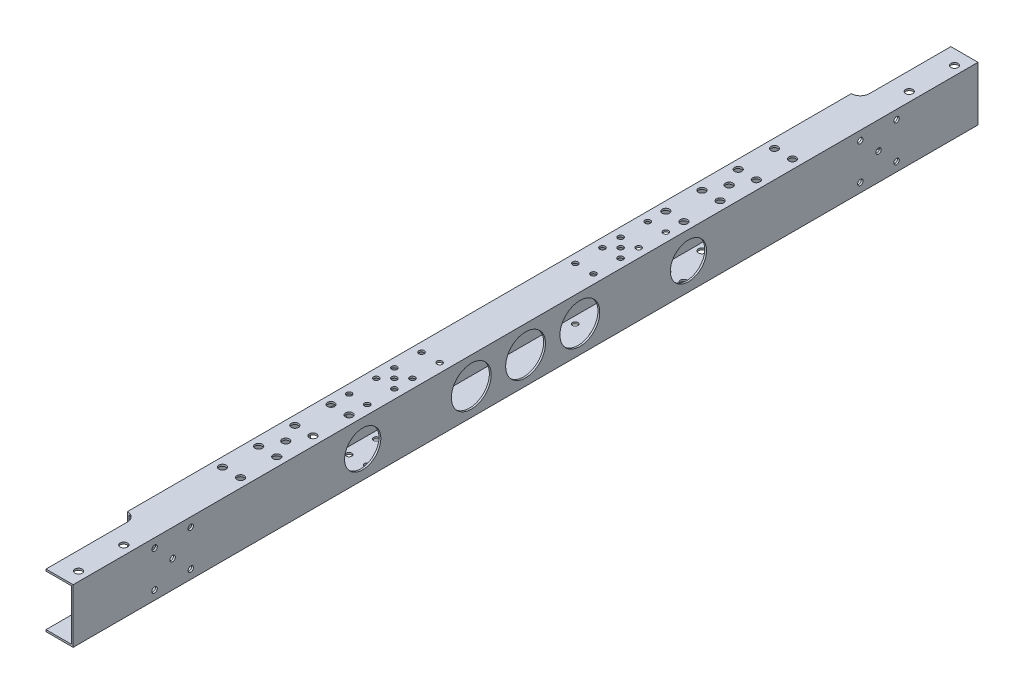
SolidWorks part; units mm, degrees
material "6061-T4 (SS)"
ref_plane "前视基准面" through (0, 0, 0) normal (0, 0, 1) x (1, 0, 0)
ref_plane "上视基准面" through (0, 0, 0) normal (0, 1, 0) x (1, 0, 0)
ref_plane "右视基准面" through (0, 0, 0) normal (1, 0, 0) x (0, 0, -1)
other "Configuration Table"
sketch "草图1" plane through (0, 0, 0) normal (0, 0, 1) x (1, 0, 0)
  line L1 (-10, -15) -> (10, -15)
  line L2 (-10, -15) -> (-10, 15)
  line L3 (-10, 15) -> (10, 15)
  line L4 (10, -15) -> (10, 15)
  line L5 (-10, -15) -> (10, 15) construction
  line L6 (-10, 15) -> (10, -15) construction
  point P0 (0, 0)
  dimension "D1" = 20
  dimension "D2" = 30
extrude "拉伸-薄壁1" add sketch "草图1" along normal blind 500 thin thin type one direction reverse wall 1
sketch "草图2" plane through (0, 15, 0) normal (0, 1, 0) x (1, 0, 0)
  line L0 (-5, -317.5) -> (5, -307.5) construction
  line L1 (-10, -500) -> (-10, 0) construction
  line L2 (0, -187.5) -> (0, -312.5) construction
  line L3 (0, -250) -> (-10, -250) construction
  line L4 (-5, -192.5) -> (5, -192.5) construction
  line L5 (-5, -192.5) -> (-5, -182.5) construction
  line L6 (-5, -182.5) -> (5, -182.5) construction
  line L7 (5, -192.5) -> (5, -182.5) construction
  line L8 (-5, -192.5) -> (5, -182.5) construction
  line L9 (-5, -182.5) -> (5, -192.5) construction
  line L10 (-5, -307.5) -> (5, -317.5) construction
  line L11 (5, -307.5) -> (5, -317.5) construction
  line L12 (-5, -317.5) -> (5, -317.5) construction
  line L13 (-5, -307.5) -> (-5, -317.5) construction
  line L14 (-5, -307.5) -> (5, -307.5) construction
  circle A0 centre (5, -182.5) radius 1.5
  circle A1 centre (5, -192.5) radius 1.5
  circle A2 centre (-5, -192.5) radius 1.5
  circle A3 centre (-5, -182.5) radius 1.5
  circle A4 centre (-5, -317.5) radius 1.5
  circle A5 centre (-5, -307.5) radius 1.5
  circle A6 centre (5, -307.5) radius 1.5
  circle A7 centre (5, -317.5) radius 1.5
  dimension "D3" = 3
  dimension "D1" = 125
  dimension "D2" = 10
  dimension "D4" = 10
extrude "切除-拉伸1" cut sketch "草图2" against normal up to surface (30 mm away) up to face at (0, -15, 250)
sketch "草图4" plane through (0, 15, 0) normal (0, 1, 0) x (1, 0, 0)
  line L0 (-10, -250) -> (52.7857, -250) construction
  line L1 (-10, -500) -> (-10, 0) construction
  line L2 (-5, -500) -> (-5, -450)
  line L3 (-10, 0) -> (-5, 0)
  line L4 (-10, 0) -> (-10, -50)
  line L5 (-10, -50) -> (-5, -50)
  line L6 (-5, 0) -> (-5, -50)
  line L7 (-10, -450) -> (-5, -450)
  line L8 (-10, -500) -> (-10, -450)
  line L9 (-10, -500) -> (-5, -500)
  dimension "D1" = 5
  dimension "D2" = 50
extrude "切除-拉伸3" cut sketch "草图4" against normal up to surface (30 mm away) up to face at (-5, -15, 319)
fillet "圆角1" radius 5 2 edges at (-5, 14.5, 450) (-5, 14.5, 50)
sketch "草图5" plane through (0, 15, 0) normal (0, 1, 0) x (1, 0, 0)
  line L0 (-10, -250) -> (78.9829, -250) construction
  line L1 (-10, -450) -> (-10, -50) construction
  line L2 (0, 0) -> (0, -20.5) construction
  line L3 (10, 0) -> (-5, 0) construction
  line L4 (-5, -33) -> (5, -33) construction
  line L5 (-5, -33) -> (-5, -8) construction
  line L6 (-5, -8) -> (5, -8) construction
  line L7 (5, -33) -> (5, -8) construction
  line L8 (-5, -33) -> (5, -8) construction
  line L9 (-5, -8) -> (5, -33) construction
  line L10 (-5, -492) -> (5, -467) construction
  line L11 (-5, -467) -> (5, -492) construction
  line L12 (5, -467) -> (5, -492) construction
  line L13 (-5, -492) -> (5, -492) construction
  line L14 (-5, -467) -> (-5, -492) construction
  line L15 (-5, -467) -> (5, -467) construction
  line L16 (0, -500) -> (0, -479.5) construction
  circle A0 centre (5, -8) radius 2
  circle A1 centre (5, -33) radius 2
  circle A2 centre (5, -467) radius 2
  circle A3 centre (5, -492) radius 2
  dimension "D2" = 4
  dimension "D1" = 25
  dimension "D3" = 8
  dimension "D4" = 10
extrude "切除-拉伸4" cut sketch "草图5" against normal up to surface (30 mm away) up to face at (-5, -15, 319)
sketch "草图6" plane through (0, 15, 0) normal (0, 1, 0) x (1, 0, 0)
  line L0 (-10, -250) -> (143.2134, -250) construction
  line L1 (-10, -450) -> (-10, -50) construction
  line L2 (-5, -182.5) -> (5, -192.5) construction
  line L3 (0, -187.5) -> (0, -127.5) construction
  line L5 (-5, -342.5) -> (5, -332.5) construction
  line L6 (-5, -137.5) -> (5, -137.5) construction
  line L7 (-5, -137.5) -> (-5, -117.5) construction
  line L8 (-5, -117.5) -> (5, -117.5) construction
  line L9 (5, -137.5) -> (5, -117.5) construction
  line L10 (-5, -137.5) -> (5, -117.5) construction
  line L11 (-5, -117.5) -> (5, -137.5) construction
  line L12 (-5, -157.5) -> (5, -157.5) construction
  line L13 (-5, -157.5) -> (-5, -97.5) construction
  line L14 (-5, -97.5) -> (5, -97.5) construction
  line L15 (5, -157.5) -> (5, -97.5) construction
  line L16 (-5, -157.5) -> (5, -97.5) construction
  line L17 (-5, -97.5) -> (5, -157.5) construction
  line L18 (-5, -167.5) -> (5, -167.5) construction
  line L19 (-5, -167.5) -> (-5, -157.5) construction
  line L20 (-5, -157.5) -> (5, -157.5) construction
  line L21 (5, -167.5) -> (5, -157.5) construction
  line L22 (-5, -167.5) -> (5, -157.5) construction
  line L23 (-5, -157.5) -> (5, -167.5) construction
  line L24 (-5, -332.5) -> (5, -342.5) construction
  line L25 (5, -332.5) -> (5, -342.5) construction
  line L26 (-5, -342.5) -> (5, -342.5) construction
  line L27 (-5, -332.5) -> (-5, -342.5) construction
  line L28 (-5, -332.5) -> (5, -332.5) construction
  line L29 (-5, -402.5) -> (5, -342.5) construction
  line L30 (-5, -342.5) -> (5, -402.5) construction
  line L31 (5, -342.5) -> (5, -402.5) construction
  line L32 (-5, -402.5) -> (5, -402.5) construction
  line L33 (-5, -342.5) -> (-5, -402.5) construction
  line L34 (-5, -342.5) -> (5, -342.5) construction
  line L35 (-5, -382.5) -> (5, -362.5) construction
  line L36 (-5, -362.5) -> (5, -382.5) construction
  line L37 (5, -362.5) -> (5, -382.5) construction
  line L38 (-5, -382.5) -> (5, -382.5) construction
  line L39 (-5, -362.5) -> (-5, -382.5) construction
  line L40 (-5, -362.5) -> (5, -362.5) construction
  line L41 (0, -312.5) -> (0, -372.5) construction
  line L42 (0, -187.5) -> (42.6444, -187.5) construction
  line L43 (-5, -207.5) -> (5, -207.5) construction
  line L44 (-5, -292.5) -> (5, -292.5) construction
  circle A0 centre (5, -97.5) radius 2
  circle A1 centre (5, -117.5) radius 2
  circle A2 centre (5, -137.5) radius 2
  circle A3 centre (5, -157.5) radius 2
  circle A4 centre (-5, -157.5) radius 2
  circle A5 centre (-5, -137.5) radius 2
  circle A6 centre (-5, -117.5) radius 2
  circle A7 centre (-5, -97.5) radius 2
  circle A8 centre (0, -127.5) radius 2
  circle A9 centre (5, -167.5) radius 1.5
  circle A10 centre (-5, -167.5) radius 1.5
  circle A11 centre (5, -182.5) radius 1.5 construction
  circle A12 centre (-5, -332.5) radius 1.5
  circle A13 centre (5, -332.5) radius 1.5
  circle A14 centre (0, -372.5) radius 2
  circle A15 centre (-5, -402.5) radius 2
  circle A16 centre (-5, -382.5) radius 2
  circle A17 centre (-5, -362.5) radius 2
  circle A18 centre (-5, -342.5) radius 2
  circle A19 centre (5, -342.5) radius 2
  circle A20 centre (5, -362.5) radius 2
  circle A21 centre (5, -382.5) radius 2
  circle A22 centre (5, -402.5) radius 2
  circle A23 centre (0, -187.5) radius 1.5
  circle A24 centre (-5, -207.5) radius 1.5
  circle A25 centre (5, -207.5) radius 1.5
  circle A26 centre (5, -292.5) radius 1.5
  circle A27 centre (-5, -292.5) radius 1.5
  circle A28 centre (0, -312.5) radius 1.5
  point P28 (0, -162.5)
  point P58 (0, -337.5)
  dimension "D3" = 4
  dimension "D4" = 3
  dimension "D1" = 20
  dimension "D2" = 60
  dimension "D5" = 10
  dimension "D6" = 15
  dimension "D7" = 10
extrude "切除-拉伸5" cut sketch "草图6" against normal up to surface (30 mm away) up to face at (5, -15, 10)
sketch "草图8" plane through (-10, 0, 0) normal (-1, 0, 0) x (0, 0, 1)
  line L0 (250, 15) -> (250, -72.2485) construction
  line L1 (450, 15) -> (50, 15) construction
  line L2 (50, 0) -> (250, 0) construction
  line L3 (50, -15) -> (50, 15) construction
  circle A0 centre (250, 0) radius 11
  circle A1 centre (280, 0) radius 11
  circle A2 centre (220, 0) radius 11
  dimension "D1" = 22
  dimension "D2" = 30
  dimension "D3" = 30
extrude "切除-拉伸6" cut sketch "草图8" against normal up to surface (20 mm away) up to face at (10, 0, 250)
sketch "草图9" plane through (10, 0, 0) normal (1, 0, 0) x (0, 0, -1)
  line L0 (-250, 0) -> (-250, 28.8218) construction
  line L2 (0, -15) -> (0, 15) construction
  line L3 (-65, -10) -> (-45, -10) construction
  line L4 (-65, -10) -> (-65, 10) construction
  line L5 (-65, 10) -> (-45, 10) construction
  line L6 (-45, -10) -> (-45, 10) construction
  line L7 (-65, -10) -> (-45, 10) construction
  line L8 (-65, 10) -> (-45, -10) construction
  line L9 (-55, 0) -> (0, 0) construction
  line L10 (-435, 10) -> (-455, -10) construction
  line L11 (-435, -10) -> (-455, 10) construction
  line L12 (-455, -10) -> (-455, 10) construction
  line L13 (-435, 10) -> (-455, 10) construction
  line L14 (-435, -10) -> (-435, 10) construction
  line L15 (-435, -10) -> (-455, -10) construction
  line L16 (-250, 0) -> (-160, 0) construction
  circle A0 centre (-250, 0) radius 11 construction
  circle A1 centre (-250, 0) radius 11 construction
  circle A2 centre (-45, 10) radius 1.5
  circle A3 centre (-45, -10) radius 1.5
  circle A4 centre (-65, -10) radius 1.5
  circle A5 centre (-65, 10) radius 1.5
  circle A6 centre (-55, 0) radius 1.5
  circle A7 centre (-445, 0) radius 1.5
  circle A8 centre (-435, 10) radius 1.5
  circle A9 centre (-435, -10) radius 1.5
  circle A10 centre (-455, -10) radius 1.5
  circle A11 centre (-455, 10) radius 1.5
  circle A12 centre (-160, 0) radius 10
  circle A13 centre (-340, 0) radius 10
  point P3 (-55, 0)
  point P29 (-445, 0)
  dimension "D2" = 3
  dimension "D4" = 20
  dimension "D5" = 90
  dimension "D1" = 55
  dimension "D3" = 20
extrude "切除-拉伸7" cut sketch "草图9" against normal up to surface (20 mm away) up to face at (-10, 0, 231)
sketch "草图10" plane through (0, 15, 0) normal (0, 1, 0) x (1, 0, 0)
  line L0 (10, -250) -> (-94.9456, -250) construction
  line L1 (10, -500) -> (10, 0) construction
  line L2 (-5, -97.5) -> (5, -97.5) construction
  line L3 (0, -97.5) -> (0, -82.5) construction
  line L4 (0, -82.5) -> (0, -57.5) construction
  line L5 (-4, -82.5) -> (-4, -57.5)
  line L6 (4, -82.5) -> (4, -57.5)
  line L7 (0, -97.5) -> (0, -109.5) construction
  line L8 (0, -109.5) -> (0, -105.5) construction
  line L9 (-4, -109.5) -> (-4, -105.5)
  line L10 (4, -109.5) -> (4, -105.5)
  line L11 (-5, -117.5) -> (5, -117.5) construction
  line L12 (0, -127.5) -> (39.9087, -127.5) construction
  line L13 (-5, -137.5) -> (5, -137.5) construction
  line L14 (0, -145.5) -> (0, -149.5) construction
  line L15 (-4, -145.5) -> (-4, -149.5)
  line L16 (4, -145.5) -> (4, -149.5)
  line L17 (0, -187.5) -> (36.5278, -187.5) construction
  line L18 (-5, -182.5) -> (5, -182.5) construction
  line L19 (-5, -167.5) -> (5, -167.5) construction
  line L20 (0, -167.5) -> (0, -182.5) construction
  line L21 (0, -332.5) -> (0, -317.5) construction
  line L22 (-5, -332.5) -> (5, -332.5) construction
  line L23 (-5, -317.5) -> (5, -317.5) construction
  line L24 (0, -312.5) -> (36.5278, -312.5) construction
  line L25 (-5, -362.5) -> (5, -362.5) construction
  line L26 (0, -372.5) -> (39.9087, -372.5) construction
  line L27 (-5, -382.5) -> (5, -382.5) construction
  line L28 (0, -402.5) -> (0, -390.5) construction
  line L29 (0, -402.5) -> (0, -417.5) construction
  line L30 (-5, -402.5) -> (5, -402.5) construction
  line L31 (0, -354.5) -> (0, -350.5) construction
  line L32 (-4, -354.5) -> (-4, -350.5)
  line L33 (4, -354.5) -> (4, -350.5)
  line L34 (0, -390.5) -> (0, -394.5) construction
  line L35 (-4, -390.5) -> (-4, -394.5)
  line L36 (4, -390.5) -> (4, -394.5)
  line L37 (0, -417.5) -> (0, -442.5) construction
  line L38 (-4, -417.5) -> (-4, -442.5)
  line L39 (4, -417.5) -> (4, -442.5)
  arc A0 (-4, -82.5) -> (4, -82.5) centre (0, -82.5) ccw
  arc A1 (4, -57.5) -> (-4, -57.5) centre (0, -57.5) ccw
  arc A2 (-4, -109.5) -> (4, -109.5) centre (0, -109.5) ccw
  arc A3 (4, -105.5) -> (-4, -105.5) centre (0, -105.5) ccw
  arc A4 (-4, -145.5) -> (4, -145.5) centre (0, -145.5) cw
  arc A5 (4, -149.5) -> (-4, -149.5) centre (0, -149.5) cw
  circle A6 centre (0, -175) radius 4
  circle A7 centre (0, -200) radius 4
  circle A8 centre (0, -325) radius 4
  arc A9 (-4, -354.5) -> (4, -354.5) centre (0, -354.5) ccw
  arc A10 (4, -350.5) -> (-4, -350.5) centre (0, -350.5) ccw
  arc A11 (-4, -390.5) -> (4, -390.5) centre (0, -390.5) cw
  arc A12 (4, -394.5) -> (-4, -394.5) centre (0, -394.5) cw
  arc A13 (-4, -417.5) -> (4, -417.5) centre (0, -417.5) cw
  arc A14 (4, -442.5) -> (-4, -442.5) centre (0, -442.5) cw
  circle A15 centre (0, -300) radius 4
  point P10 (0, -70)
  point P17 (0, -107.5)
  point P35 (0, -147.5)
  point P80 (0, -352.5)
  point P86 (0, -392.5)
  point P92 (0, -430)
  dimension "D2" = 4
  dimension "D5" = 8
  dimension "D6" = 8
  dimension "D1" = 25
  dimension "D3" = 15
  dimension "D4" = 8
extrude "切除-拉伸8" [suppressed] cut sketch "草图10" against normal blind 55
